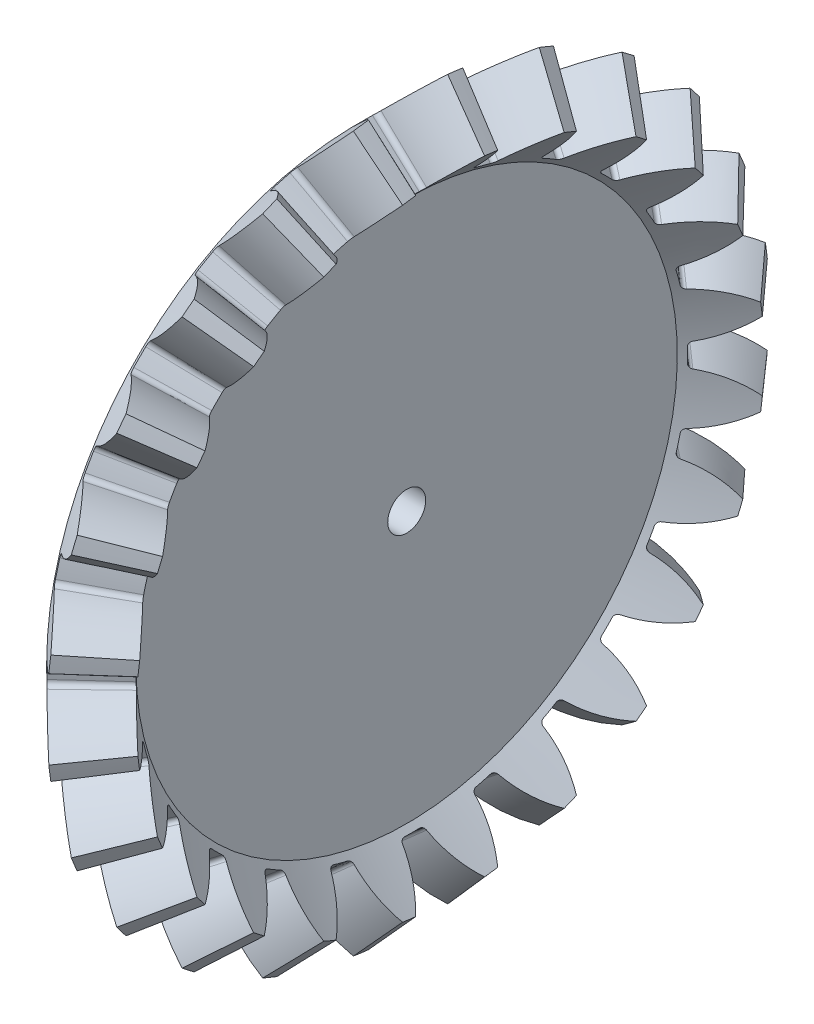
SolidWorks part; units mm, degrees
revolve "Base-Revolve" add sketch "BasProSke" angle 360 about L0 other way angle 7.5
sketch "BasProSke" plane through (0, 0, 0) normal (0, 1, 0) x (1, 0, 0)
  line L0 (-10, 0) -> (60, 0) construction
  line L1 (0, 0) -> (0, 24.6365)
  line L2 (0, 0) -> (3.845, 0)
  line L3 (3.845, 0) -> (3.845, 21.4105)
  line L4 (29.3635, 0) -> (-20.0585, 49.422) construction
  line L5 (0, 24.6365) -> (3.9545, 28.591)
  line L6 (29.3635, 0) -> (-44.1573, 82.7278) construction
  line L7 (29.3635, 0) -> (0, 24.6365) construction
  line L8 (3.9545, 28.591) -> (7.2817, 24.8471)
  line L9 (7.2817, 24.8471) -> (3.845, 21.4105)
  line L10 (2.3635, 27) -> (-9.6208, 27) construction
  dimension "D1" = 49.273
  dimension "D2" = 29.3635
  dimension "D3" = 38.1838
  dimension "D4" = 3.372
ref_plane "Plane1" through (0, 0, 0) normal (0, 0, 1) x (1, 0, 0)
ref_plane "Plane2" through (0, 0, 0) normal (0, 1, 0) x (1, 0, 0)
ref_plane "Plane3" through (0, 0, 0) normal (1, 0, 0) x (0, 0, -1)
other "Configuration Table"
sketch "HoldingSke" plane through (0, 0, 0) normal (0, 1, 0) x (1, 0, 0)
  line L0 (0, 0) -> (0.406, -0.1808)
  line L1 (-15, 0) -> (100, 0) construction
  line L2 (0, 0) -> (-90.9974, 40.8499)
  line L3 (0, 0) -> (-11.863, 4.5341)
  line L4 (0, 0) -> (7.8894, 3.5126)
  line L5 (0, 0) -> (-9.3695, -3.4946)
  line L6 (0, 0) -> (-10.5278, -7.1032)
  line L7 (-90.9974, 40.8499) -> (-84.6769, 69.5252)
  line L8 (-76.2, 2.25) -> (-75.7, 2.25)
  line L9 (-71.009, 38.7566) -> (-53.1078, 45.2721)
  line L10 (-76.2, 71.12) -> (104.1128, 71.12)
  line L11 (0, 0) -> (-5, 0)
  line L12 (-76.2, 101.6) -> (-76.123, 101.6)
  line L13 (24.9733, 27.94) -> (52.9518, 28.4284)
  line L14 (24.9733, 27.94) -> (24.9743, 27.94)
  line L15 (24.9733, 27.94) -> (100.4024, 29.5042)
  line L16 (-90.9974, 40.8499) -> (26.948, -11.6628)
  circle A0 centre (0, 0) radius 1.5
  circle A1 centre (0, 0) radius 5
  circle A2 centre (0, 0) radius 5
  circle A3 centre (0, 0) radius 1.5
  dimension "Num_teeth" = 24
  dimension "Pitch_radius" = 180.3128
  dimension "Width" = 5
ref_plane "ToothPln" through (1.9772, 26.6137, 0) normal (-0.7071, 0.7071, 0) x (0, 0, -1)
ref_plane "ToothPln2" through (14.6818, -14.6818, 0) normal (-0.7071, 0.7071, 0) x (0, 0, 1)
sketch "TooCutSke" plane through (1.9772, 26.6137, 0) normal (-0.7071, 0.7071, 0) x (0, 0, -1)
  line L2 (0, 26.4538) -> (221.7879, -1658.1923) construction
  line L3 (0, 26.4538) -> (119.7249, -1761.0552) construction
  line L4 (0, -15.621) -> (0, 105.791) construction
  line L6 (-24.765, -2.7963) -> (21.082, -2.7963) construction
  line L7 (3.5242, -0.3153) -> (1.8007, -0.4307) construction
  arc A0 (-3.5434, -3.1701) -> (3.5434, -3.1701) centre (0, 26.4538) ccw
  arc A1 (-0.6665, 2.1369) -> (0.6665, 2.1369) centre (0, 26.4538) ccw
  circle A2 centre (0, 26.4538) radius 27 construction
  circle A3 centre (0, 26.4538) radius 25.3717 construction
  arc A4 (1.0937, 1.7968) -> (0.6665, 2.1369) centre (0.6781, 1.713) ccw
  arc A5 (1.0937, 1.7968) -> (3.5434, -3.1701) centre (11.6808, 3.9308) ccw
  arc A6 (-3.5434, -3.1701) -> (-1.0937, 1.7968) centre (-11.6808, 3.9308) ccw
  arc A7 (-0.6665, 2.1369) -> (-1.0937, 1.7968) centre (-0.6781, 1.713) ccw
  ellipse E0 centre (0, 17.4206) end of major axis (28.591, 17.4206) minor radius 20.2169 construction
sketch "TooCutSke2" plane through (14.6818, -14.6818, 0) normal (-0.7071, 0.7071, 0) x (0, 0, 1)
  line L0 (0, 0) -> (0, 68.072) construction
  line L2 (21.082, 17.4206) -> (-20.32, 17.4206) construction
  circle A0 centre (0, 20.7631) radius 0.0127
  ellipse E1 centre (0, 0) end of major axis (-24.6365, 0) minor radius 17.4206 construction
loft "ToothCut" cut profiles "TooCutSke2", "TooCutSke"
pattern_circular "TeethCuts" count 24 every 15 about axis through (-10, 0, 0) along (1, 0, 0) of "ToothCut"
sketch "HubSke" plane through (0, 0, 0) normal (-1, 0, 0) x (0, 0, 1)
  circle A0 centre (0, 0) radius 5
  dimension "Diameter" = 10
extrude "Hub" add sketch "HubSke" along normal blind 0.0001
sketch "BorSke" plane through (0, 0, 0) normal (1, 0, 0) x (0, 0, -1)
  circle A0 centre (0, 0) radius 1.5
  dimension "Diameter" = 3
extrude "Bore" cut sketch "BorSke" along normal mid plane 58.7271
sketch "KeySke" plane through (0, 0, 0) normal (1, 0, 0) x (0, 0, -1)
  line L0 (-0.6, 0) -> (-0.6, 2)
  line L1 (-0.6, 2) -> (0.6, 2)
  line L2 (0.6, 2) -> (0.6, 0)
  line L3 (0, 0) -> (0, 34) construction
  line L4 (-0.6, 0) -> (0.6, 0)
  dimension "Offset" = 2
extrude "Keyway" [suppressed] cut sketch "KeySke" along normal mid plane 58.7271
pattern_circular "Keyway2" [suppressed] count 2 every 90 about axis through (-10, 0, 0) along (1, 0, 0)
equation "' \"Module@HoldingSke\" = 6.35"
equation "' \"Num_teeth@HoldingSke\" = 12"
equation "' \"Mating_teeth@HoldingSke\" = 12"
equation "' \"Ap@HoldingSke\" =  20"
equation "' \"Ap@HoldingSke\" = 20"
equation "' \"Width@HoldingSke\" = 0.5 * 25.4"
equation "' \"Hub_dia@HoldingSke\"= 2 * 25.4"
equation "' \"Hub_dia@HoldingSke\" = 2 * 25.4"
equation "' \"Mounting_dist@HoldingSke\" = 2 * 25.4"
equation "' \"Bore@HoldingSke\" = 19"
equation "' \"T_dim@HoldingSke\" = 0.1 * 25.4"
equation "' \"Width@KeySke\" = 0.25 * 25.4"
equation "' \"Show_teeth@HoldingSke\" = 100"
equation "' \"Backlash@HoldingSke\" = 0.009 * 25.4"
equation "' \"Addendum_fac@HoldingSke\" = 1.0"
equation "' \"Dedendum_fac@HoldingSke\" = 1.188"
equation "' \"Dedendum_add@HoldingSke\" = 0.002 * 25.4"
equation "' \"Clearance_fac@HoldingSke\" = 0.188"
equation "\"Pitch@HoldingSke\" = 1 / \"Module@HoldingSke\""
equation "' \"Addendum_fac@HoldingSke\" = 0.54 + 0.46 / (\"Num_teeth@HoldingSke\" /  \"Mating_teeth@HoldingSke\" ) ^ 2"
equation " \"Addendum_fac@HoldingSke\" = 2 - (0.54 + 0.46 / (\"Mating_teeth@HoldingSke\" /  \"Num_teeth@HoldingSke\" ) ^ 2)"
equation "\"Dedendum_fac@HoldingSke\" = 2.188 - \"Addendum_fac@HoldingSke\""
equation "\"Pitch_rad@BasProSke\" = \"Num_teeth@HoldingSke\" / \"Pitch@HoldingSke\" / 2"
equation "\"Pitch_ang@BasProSke\" = atn(\"Num_teeth@HoldingSke\" / \"Mating_teeth@HoldingSke\") * (180 / 3.14159265)"
equation "\"Addendum@BasProSke\" = \"Addendum_fac@HoldingSke\" / \"Pitch@HoldingSke\""
equation "\"Dedendum_plus@BasProSke\" = (\"Dedendum_fac@HoldingSke\" / \"Pitch@HoldingSke\" + \"Dedendum_add@HoldingSke\") * 1.25"
equation "\"Face_wid@BasProSke\" = \"Width@HoldingSke\""
equation "\"Radius@TooCutSke\" = ((\"Num_teeth@HoldingSke\" + 2 * \"Addendum_fac@HoldingSke\") / \"Pitch@HoldingSke\" ) / 2"
equation "\"Overcut_dia@TooCutSke\" =  1.02 * (\"Num_teeth@HoldingSke\" + 2 * \"Addendum_fac@HoldingSke\") / \"Pitch@HoldingSke\""
equation "\"Pitch_dia@TooCutSke\" = \"Num_teeth@HoldingSke\" / \"Pitch@HoldingSke\""
equation "\"Base_dia@TooCutSke\" = \"Num_teeth@HoldingSke\" / \"Pitch@HoldingSke\" * cos((\"Ap@HoldingSke\"  * 3.14159265 / 180))"
equation "'  \"Root_dia@TooCutSke\" =  (\"Num_teeth@HoldingSke\" + 2) / \"Pitch@HoldingSke\" - 2 * (\"Addendum_fac@HoldingSke\" + \"Dedendum_fac@HoldingSke\") / \"Pitch@HoldingSke\" - \"Dedendum_add@HoldingSke\" * 2"
equation "'  \"Root_dia@TooCutSke\" = (\"Num_teeth@HoldingSke\" + 2) / \"Pitch@HoldingSke\" - 2 * (\"Addendum_fac@HoldingSke\" + \"Dedendum_fac@HoldingSke\") / \"Pitch@HoldingSke\" - \"Dedendum_add@HoldingSke\" * 2"
equation "\"Root_dia@TooCutSke\" =  \"Num_teeth@HoldingSke\" / \"Pitch@HoldingSke\" -  2 * \"Dedendum_fac@HoldingSke\" / \"Pitch@HoldingSke\" - \"Dedendum_add@HoldingSke\" * 2"
equation "\"Half_ang@TooCutSke\" = 180 / \"Num_teeth@HoldingSke\""
equation "\"Half_CT@TooCutSke\" = \"Num_teeth@HoldingSke\" / \"Pitch@HoldingSke\" * sin((3.14159265 / 2 / \"Num_teeth@HoldingSke\")) / 2 - 2 * \"Backlash@HoldingSke\" / 4"
equation "\"Flank_rad@TooCutSke\" = \"Num_teeth@HoldingSke\" / \"Pitch@HoldingSke\" / 5"
equation "\"Root_fillet@TooCutSke\" = \"Clearance_fac@HoldingSke\" / \"Pitch@HoldingSke\" + \"Dedendum_add@HoldingSke\""
equation "\"Offset@ToothPln2\"  = \"Num_teeth@HoldingSke\" / \"Pitch@HoldingSke\" / 2 / sin(atn(\"Num_teeth@HoldingSke\" / \"Mating_teeth@HoldingSke\"))"
equation "\"Dedendum_plus@TooCutSke2\" = \"Dedendum_plus@BasProSke\""
equation "\"MHD@HoldingSke\" = \"Num_teeth@HoldingSke\" / \"Pitch@HoldingSke\" - 2 * \"Dedendum_plus@BasProSke\" * cos(atn(\"Num_teeth@HoldingSke\" / \"Mating_teeth@HoldingSke\"))"
equation "\"MBD@HoldingSke\" = \"Num_teeth@HoldingSke\" / \"Pitch@HoldingSke\" - 2 * \"Dedendum_plus@BasProSke\" * cos(atn(\"Num_teeth@HoldingSke\" / \"Mating_teeth@HoldingSke\")) - 0.002 * 25.4"
equation "\"MnMD@HoldingSke\" =  \"Num_teeth@HoldingSke\" / \"Pitch@HoldingSke\" / 2 / (\"Num_teeth@HoldingSke\" / \"Mating_teeth@HoldingSke\") + \"Dedendum_plus@BasProSke\" * sin(atn(\"Num_teeth@HoldingSke\" / \"Mating_teeth@HoldingSke\"))"
equation "\"OAL@HoldingSke\" = \"MnMD@HoldingSke\""
equation "\"MHD@HoldingSke\" = ((sgn( \"MHD@HoldingSke\" - \"Hub_dia@HoldingSke\" )-1)*( \"MHD@HoldingSke\" - \"Hub_dia@HoldingSke\" ))/-2+ \"Hub_dia@HoldingSke\""
equation "\"MBD@HoldingSke\" = ((sgn( \"MBD@HoldingSke\" - \"Bore@HoldingSke\" )-1)*( \"MBD@HoldingSke\" - \"Bore@HoldingSke\" ))/-2+ \"Bore@HoldingSke\""
equation "\"Face_wid@BasProSke\" = ((sgn( \"Face_wid@BasProSke\" - \"Offset@ToothPln2\" * 0.9)-1)*( \"Face_wid@BasProSke\" - \"Offset@ToothPln2\" * 0.9))/-2+ \"Offset@ToothPln2\" * 0.9"
equation "\"OAL@HoldingSke\" = ((sgn( \"OAL@HoldingSke\" - \"Mounting_dist@HoldingSke\" )+1)*( \"OAL@HoldingSke\" - \"Mounting_dist@HoldingSke\" ))/2 + \"Mounting_dist@HoldingSke\" + 0.000002 * 25.4"
equation "\"Num_teeth@TeethCuts\" = int( \"Show_teeth@HoldingSke\" ) + 1"
equation "\"Num_teeth@TeethCuts\" = ((sgn( \"Num_teeth@TeethCuts\" - \"Num_teeth@HoldingSke\" )-1)*( \"Num_teeth@TeethCuts\" - \"Num_teeth@HoldingSke\" ))/-2+ \"Num_teeth@HoldingSke\""
equation "\"Num_teeth@TeethCuts\" = ((sgn( \"Num_teeth@TeethCuts\" - 2.0)+1)*( \"Num_teeth@TeethCuts\" - 2.0))/2 +2.0"
equation "\"Angle@TeethCuts\" = 360.0 / \"Num_teeth@HoldingSke\""
equation "\"Diameter@HubSke\" = \"MHD@HoldingSke\""
equation "\"Length@Hub\" = \"OAL@HoldingSke\" - \"MnMD@HoldingSke\" + 0.000002 * 25.4"
equation "\"Diameter@BorSke\" = \"MBD@HoldingSke\""
equation "\"D1@Bore\" = \"OAL@HoldingSke\" * 2.0"
equation "\"D1@Keyway\" = \"OAL@HoldingSke\" * 2.0"
equation "\"Offset@KeySke\" = \"T_dim@HoldingSke\" + \"MBD@HoldingSke\" / 2.0"
